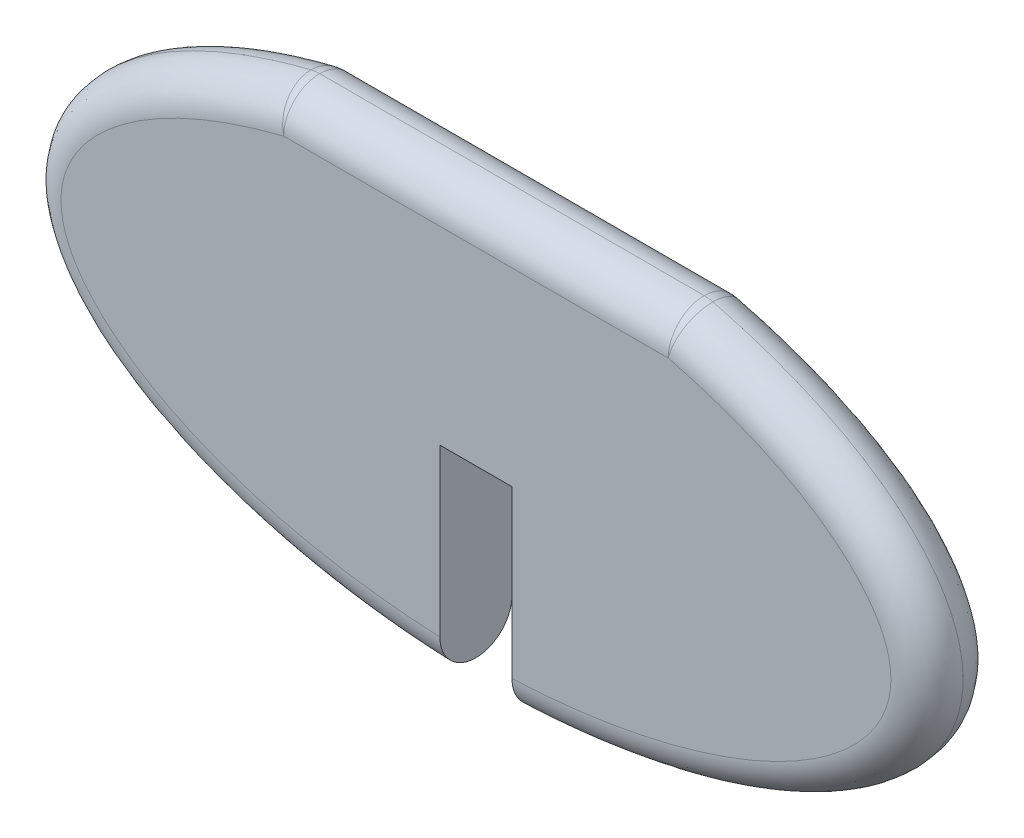
SolidWorks part; units mm, degrees
ref_plane "前基準面" through (0, 0, 0) normal (0, 0, 1) x (1, 0, 0)
ref_plane "上基準面" through (0, 0, 0) normal (0, 1, 0) x (1, 0, 0)
ref_plane "右基準面" through (0, 0, 0) normal (1, 0, 0) x (0, 0, -1)
sketch "草圖1" plane through (0, 0, 0) normal (0, 0, 1) x (1, 0, 0)
  line L0 (-21.7945, 22.5) -> (21.7945, 22.5)
  line L6 (-3.999, -2.5) -> (4.001, -2.5)
  line L7 (-3.999, -2.5) -> (-3.999, -24.9199)
  line L9 (4.001, -2.5) -> (4.001, -24.9198)
  ellipse E0 centre (0, 0) end of major axis (50, 0) minor radius 25 (-21.7945, 22.5) -> (-3.999, -24.9199) ccw
  ellipse E1 centre (0, 0) end of major axis (50, 0) minor radius 25 (4.001, -24.9198) -> (21.7945, 22.5) ccw
  point P2 (0, -15)
  dimension "D1" = 50
  dimension "D2" = 25
  dimension "D3" = 22.5
  dimension "D4" = 8
extrude "填料-伸長1" add sketch "草圖1" along normal blind 8
fillet "圓角1" radius 4 2 edges at (21.7945, 22.5, 4) (-21.7945, 22.5, 4)
fillet "圓角2" radius 4 10 edges at (49.0923, -4.7419, 0) (21.7973, 22.4703, 0) (-49.0921, -4.7424, 0) (-21.7973, 22.4703, 0) (49.0923, -4.7419, 8) (21.7973, 22.4703, 8) (-49.0921, -4.7424, 8) (-21.7973, 22.4703, 8) (0, 22.5, 0) (0, 22.5, 8)
